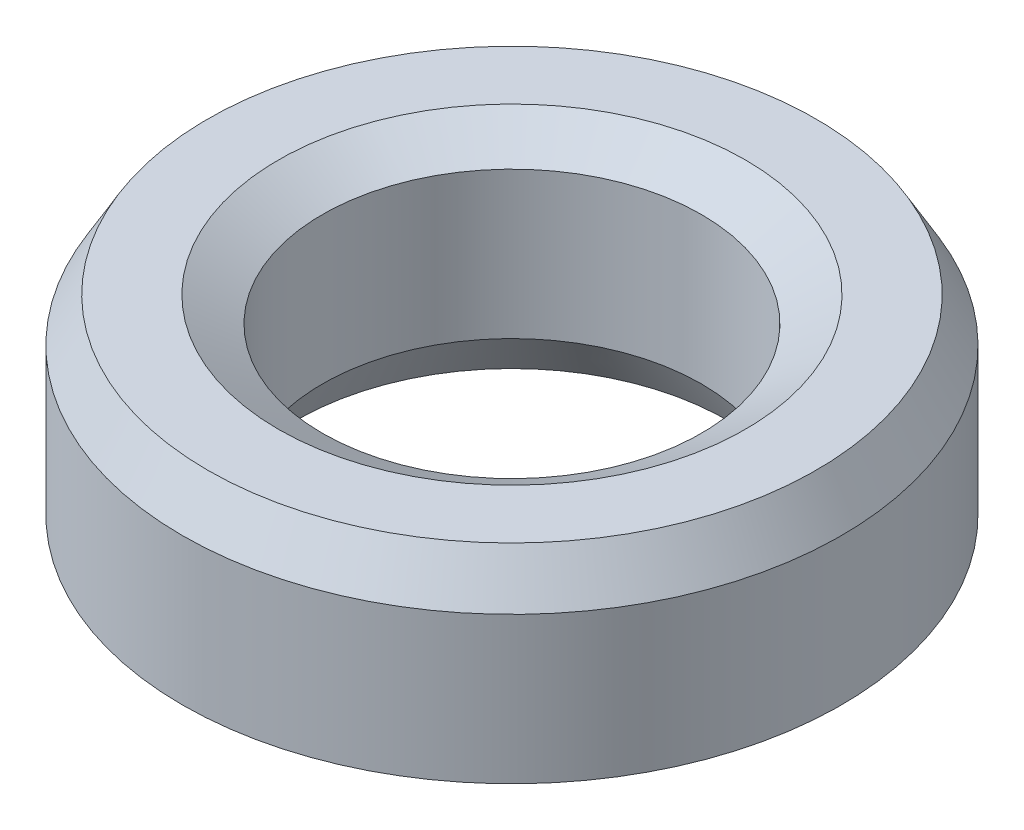
SolidWorks part; units mm, degrees
ref_plane "Front Plane" through (0, 0, 0) normal (0, 0, 1) x (1, 0, 0)
ref_plane "Top Plane" through (0, 0, 0) normal (0, 1, 0) x (1, 0, 0)
ref_plane "Right Plane" through (0, 0, 0) normal (1, 0, 0) x (0, 0, -1)
sketch "Sketch1" plane through (0, 0, 0) normal (0, 1, 0) x (1, 0, 0)
  circle A0 centre (0, 0) radius 25
  dimension "SLEEVE_OD" = 50
extrude "Boss-Extrude1" add sketch "Sketch1" along normal blind 16.3807
sketch "Sketch2" plane through (0, 0, 0) normal (0, 1, 0) x (1, 0, 0)
  circle A0 centre (0, 0) radius 14.3764
  dimension "BORE_D" = 28.7528
extrude "Cut-Extrude1" cut sketch "Sketch2" along normal through all
chamfer "Chamfer1" distance 3.3295 angle 30 4 edges at (0, 16.3807, 14.3764) (0, 0, 14.3764) (0, 0, 25) (0, 16.3807, 25) first distance on face at (0, 16.3807, 14.3764) first distance on face at (0, 0, 14.3764) first distance on face at (0, 16.3807, 25)
